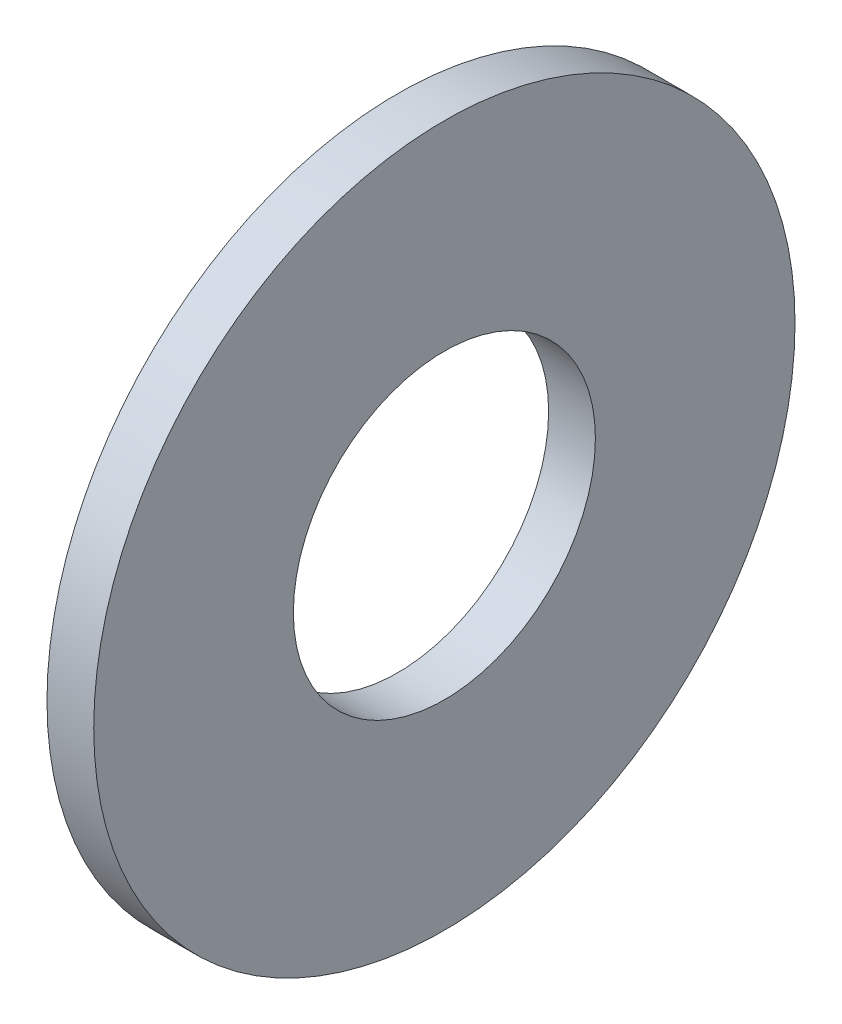
SolidWorks part; units mm, degrees
ref_plane "Front Plane" through (0, 0, 0) normal (0, 0, 1) x (1, 0, 0)
ref_plane "Top Plane" through (0, 0, 0) normal (0, 1, 0) x (1, 0, 0)
ref_plane "Right Plane" through (0, 0, 0) normal (1, 0, 0) x (0, 0, -1)
sketch "Sketch1" plane through (0, 0, 0) normal (1, 0, 0) x (0, 0, -1)
  circle A0 centre (0, 0) radius 4.1021
  circle A1 centre (0, 0) radius 9.525
  dimension "D1" = 19.05
  dimension "D2" = 8.2042
extrude "Boss-Extrude1" add sketch "Sketch1" along normal blind 1.27
